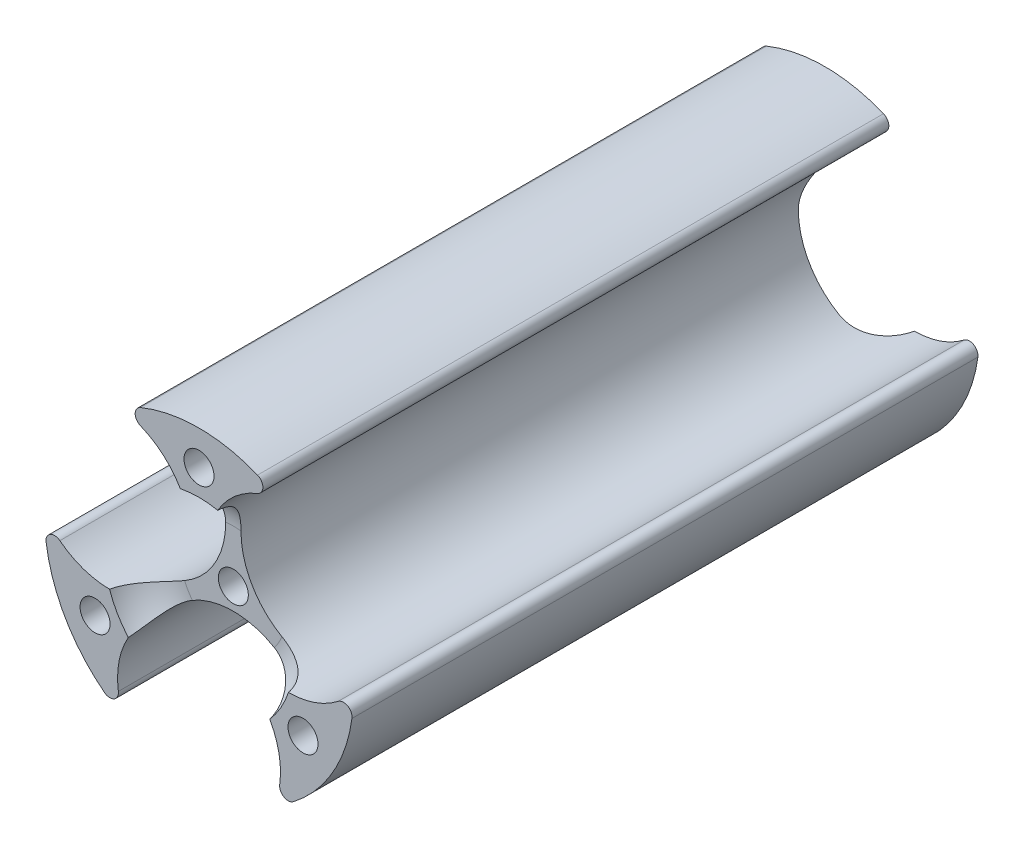
SolidWorks part; units mm, degrees
material "ABS"
ref_plane "Спереди" through (0, 0, 0) normal (0, 0, 1) x (1, 0, 0)
ref_plane "Сверху" through (0, 0, 0) normal (0, 1, 0) x (1, 0, 0)
ref_plane "Справа" through (0, 0, 0) normal (1, 0, 0) x (0, 0, -1)
sketch "Эскиз1" plane through (0, 0, 0) normal (0, 0, 1) x (1, 0, 0)
  line L0 (0, 0) -> (0, -18) construction
  line L1 (0, 0) -> (0, 18) construction
  circle A0 centre (0, 0) radius 18
  circle A1 centre (0, -12) radius 9.5
  circle A2 centre (-10.3923, 6) radius 9.5
  circle A3 centre (10.3923, 6) radius 9.5
  circle A4 centre (0, 14) radius 1.75
  circle A5 centre (12.1244, -7) radius 1.75
  circle A6 centre (-12.1244, -7) radius 1.75
  circle A7 centre (0, 0) radius 1.75
  point P13 (0, 0)
  point P20 (0, 0)
  dimension "D1" = 19
  dimension "D4" = 36
  dimension "D5" = 3.5
  dimension "D7" = 3.5
  dimension "D2" = 12
  dimension "D6" = 14
  dimension "D3" = 3
extrude "Бобышка-Вытянуть1" add sketch "Эскиз1" along normal blind 65 contours A3 A0 A2 A1 region at (15.086, -8.8822, 0)
fillet "Скругление1" radius 1 6 edges at (17.9974, 0.3068, 32.5) (8.733, -15.7396, 32.5) (-8.733, -15.7396, 32.5) (-17.9974, 0.3068, 32.5) (-9.2644, 15.4328, 32.5) (9.2644, 15.4328, 32.5)
sketch "Эскиз2" plane through (0, 0, 65) normal (0, 0, 1) x (1, 0, 0)
  arc A0 (6.8256, 16.6557) -> (-6.8256, 16.6557) centre (0, 0) ccw
  circle A1 centre (0, 14) radius 1.75
  circle A2 centre (0, 14) radius 1.75
  circle A3 centre (10.3923, 6) radius 9.5
  arc A4 (6.8222, 14.8037) -> (16.2314, -1.4936) centre (10.3923, 6) ccw
  circle A5 centre (-10.3923, 6) radius 9.5
  arc A6 (-16.2314, -1.4936) -> (-6.8222, 14.8037) centre (-10.3923, 6) ccw
  circle A7 centre (0, -12) radius 9.5
  arc A8 (9.4092, -13.31) -> (-9.4092, -13.31) centre (0, -12) ccw
  circle A9 centre (0, 0) radius 18
  arc A10 (-17.837, -2.4167) -> (-11.0114, -14.239) centre (0, 0) ccw
  circle A11 centre (0, 0) radius 1.75
  arc A12 (11.0114, -14.239) -> (17.837, -2.4167) centre (0, 0) ccw
  arc A13 (17.837, -2.4167) -> (16.2314, -1.4936) centre (16.8461, -2.2824) ccw
  arc A14 (6.8222, 14.8037) -> (16.2314, -1.4936) centre (10.3923, 6) ccw
  arc A15 (6.8222, 14.8037) -> (6.8256, 16.6557) centre (6.4464, 15.7304) ccw
  arc A16 (6.8256, 16.6557) -> (-6.8256, 16.6557) centre (0, 0) ccw
  arc A17 (-6.8256, 16.6557) -> (-6.8222, 14.8037) centre (-6.4464, 15.7304) ccw
  arc A18 (-16.2314, -1.4936) -> (-6.8222, 14.8037) centre (-10.3923, 6) ccw
  arc A19 (-16.2314, -1.4936) -> (-17.837, -2.4167) centre (-16.8461, -2.2824) ccw
  arc A20 (-17.837, -2.4167) -> (-11.0114, -14.239) centre (0, 0) ccw
  arc A21 (-11.0114, -14.239) -> (-9.4092, -13.31) centre (-10.3997, -13.4479) ccw
  arc A22 (9.4092, -13.31) -> (-9.4092, -13.31) centre (0, -12) ccw
  arc A23 (9.4092, -13.31) -> (11.0114, -14.239) centre (10.3997, -13.4479) ccw
  arc A24 (11.0114, -14.239) -> (17.837, -2.4167) centre (0, 0) ccw
  arc A25 (17.837, -2.4167) -> (16.2314, -1.4936) centre (16.8461, -2.2824) ccw
  arc A26 (6.8222, 14.8037) -> (16.2314, -1.4936) centre (10.3923, 6) ccw
  arc A27 (6.8222, 14.8037) -> (6.8256, 16.6557) centre (6.4464, 15.7304) ccw
  arc A28 (6.8256, 16.6557) -> (-6.8256, 16.6557) centre (0, 0) ccw
  arc A29 (-6.8256, 16.6557) -> (-6.8222, 14.8037) centre (-6.4464, 15.7304) ccw
  arc A30 (-16.2314, -1.4936) -> (-6.8222, 14.8037) centre (-10.3923, 6) ccw
  arc A31 (-16.2314, -1.4936) -> (-17.837, -2.4167) centre (-16.8461, -2.2824) ccw
  arc A32 (-17.837, -2.4167) -> (-11.0114, -14.239) centre (0, 0) ccw
  arc A33 (-11.0114, -14.239) -> (-9.4092, -13.31) centre (-10.3997, -13.4479) ccw
  arc A34 (9.4092, -13.31) -> (-9.4092, -13.31) centre (0, -12) ccw
  arc A35 (9.4092, -13.31) -> (11.0114, -14.239) centre (10.3997, -13.4479) ccw
  circle A36 centre (0, 0) radius 1.75
  circle A37 centre (-12.1244, -7) radius 1.75
  circle A38 centre (-12.1244, -7) radius 1.75
  circle A39 centre (12.1244, -7) radius 1.75
  circle A40 centre (12.1244, -7) radius 1.75
  arc A41 (11.0114, -14.239) -> (17.837, -2.4167) centre (0, 0) ccw
  circle A42 centre (0, 0) radius 11
  circle M23 centre (-12.1244, -7) radius 1.75
  circle M24 centre (12.1244, -7) radius 1.75
  circle M25 centre (0, 14) radius 1.75
  arc M26 (11.0114, -14.239) -> (17.837, -2.4167) centre (0, 0) ccw
  arc M27 (17.837, -2.4167) -> (16.2314, -1.4936) centre (16.8461, -2.2824) ccw
  arc M28 (16.2314, -1.4936) -> (6.8222, 14.8037) centre (10.3923, 6) cw
  arc M29 (6.8222, 14.8037) -> (6.8256, 16.6557) centre (6.4464, 15.7304) ccw
  arc M30 (6.8256, 16.6557) -> (-6.8256, 16.6557) centre (0, 0) ccw
  arc M31 (-6.8256, 16.6557) -> (-6.8222, 14.8037) centre (-6.4464, 15.7304) ccw
  arc M32 (-6.8222, 14.8037) -> (-16.2314, -1.4936) centre (-10.3923, 6) cw
  arc M33 (-16.2314, -1.4936) -> (-17.837, -2.4167) centre (-16.8461, -2.2824) ccw
  arc M34 (-17.837, -2.4167) -> (-11.0114, -14.239) centre (0, 0) ccw
  arc M35 (-11.0114, -14.239) -> (-9.4092, -13.31) centre (-10.3997, -13.4479) ccw
  arc M36 (-9.4092, -13.31) -> (9.4092, -13.31) centre (0, -12) cw
  arc M37 (9.4092, -13.31) -> (11.0114, -14.239) centre (10.3997, -13.4479) ccw
  dimension "D10" = 22
  dimension "D1" = 0
  dimension "D2" = 0
  dimension "D3" = 0
  dimension "D4" = 0
  dimension "D5" = 0
  dimension "D6" = 0
  dimension "D7" = 0
  dimension "D8" = 0
  dimension "D9" = 0
extrude "Бобышка-Вытянуть2" add sketch "Эскиз2" along normal blind 4 contours A42 M28 M29 M30 M31 M32 M25 | A42 M36 M37 M26 M27 M28 M24 | A42 M32 M33 M34 M35 M36 M23 region at (7.2809, 15.7288, 65) region at (17.2633, -1.5568, 65) region at (-13.5497, -3.1325, 65)
fillet "Скругление2" radius 5 3 edges at (-9.5263, -5.5, 65) (9.5263, -5.5, 65) (0, 11, 65)
sketch "Эскиз3" plane through (0, 0, 0) normal (0, 0, -1) x (-1, 0, 0)
  arc A0 (-17.837, -2.4167) -> (-11.0114, -14.239) centre (0, 0) ccw construction
  circle A1 centre (0, 0) radius 11
  circle A2 centre (0, 0) radius 11
  circle A3 centre (0, 14) radius 1.75
  circle A4 centre (0, 14) radius 1.75
  circle A5 centre (12.1244, -7) radius 1.75
  circle A6 centre (12.1244, -7) radius 1.75
  circle A7 centre (0, 0) radius 1.75
  circle A8 centre (0, 0) radius 1.75
  circle A9 centre (-12.1244, -7) radius 1.75
  circle A10 centre (-12.1244, -7) radius 1.75
  arc A11 (-16.2314, -1.4936) -> (-17.837, -2.4167) centre (-16.8461, -2.2824) ccw construction
  arc A12 (-17.837, -2.4167) -> (-11.0114, -14.239) centre (0, 0) ccw construction
  arc A13 (-11.0114, -14.239) -> (-9.4092, -13.31) centre (-10.3997, -13.4479) ccw construction
  arc A14 (-16.2314, -1.4936) -> (-6.8222, 14.8037) centre (-10.3923, 6) ccw construction
  arc A15 (-16.2314, -1.4936) -> (-6.8222, 14.8037) centre (-10.3923, 6) ccw construction
  arc A16 (-6.8256, 16.6557) -> (-6.8222, 14.8037) centre (-6.4464, 15.7304) ccw construction
  arc A17 (6.8256, 16.6557) -> (-6.8256, 16.6557) centre (0, 0) ccw construction
  arc A18 (6.8256, 16.6557) -> (-6.8256, 16.6557) centre (0, 0) ccw construction
  arc A19 (6.8222, 14.8037) -> (6.8256, 16.6557) centre (6.4464, 15.7304) ccw construction
  arc A20 (11.0114, -14.239) -> (17.837, -2.4167) centre (0, 0) ccw construction
  arc A21 (11.0114, -14.239) -> (17.837, -2.4167) centre (0, 0) ccw construction
  arc A22 (9.4092, -13.31) -> (11.0114, -14.239) centre (10.3997, -13.4479) ccw construction
  arc A23 (17.837, -2.4167) -> (16.2314, -1.4936) centre (16.8461, -2.2824) ccw construction
  arc A24 (9.4092, -13.31) -> (-9.4092, -13.31) centre (0, -12) ccw construction
  arc A25 (9.4092, -13.31) -> (-9.4092, -13.31) centre (0, -12) ccw construction
  arc A26 (6.8222, 14.8037) -> (16.2314, -1.4936) centre (10.3923, 6) ccw construction
  arc A27 (6.8222, 14.8037) -> (16.2314, -1.4936) centre (10.3923, 6) ccw construction
  arc A28 (-17.837, -2.4167) -> (-11.0114, -14.239) centre (0, 0) ccw
  arc A29 (-16.2314, -1.4936) -> (-17.837, -2.4167) centre (-16.8461, -2.2824) ccw
  arc A30 (-17.837, -2.4167) -> (-11.0114, -14.239) centre (0, 0) ccw
  arc A31 (-11.0114, -14.239) -> (-9.4092, -13.31) centre (-10.3997, -13.4479) ccw
  arc A32 (-16.2314, -1.4936) -> (-6.8222, 14.8037) centre (-10.3923, 6) ccw
  arc A33 (-16.2314, -1.4936) -> (-6.8222, 14.8037) centre (-10.3923, 6) ccw
  arc A34 (-6.8256, 16.6557) -> (-6.8222, 14.8037) centre (-6.4464, 15.7304) ccw
  arc A35 (6.8256, 16.6557) -> (-6.8256, 16.6557) centre (0, 0) ccw
  arc A36 (6.8256, 16.6557) -> (-6.8256, 16.6557) centre (0, 0) ccw
  arc A37 (6.8222, 14.8037) -> (6.8256, 16.6557) centre (6.4464, 15.7304) ccw
  arc A38 (11.0114, -14.239) -> (17.837, -2.4167) centre (0, 0) ccw
  arc A39 (11.0114, -14.239) -> (17.837, -2.4167) centre (0, 0) ccw
  arc A40 (9.4092, -13.31) -> (11.0114, -14.239) centre (10.3997, -13.4479) ccw
  arc A41 (17.837, -2.4167) -> (16.2314, -1.4936) centre (16.8461, -2.2824) ccw
  arc A42 (9.4092, -13.31) -> (-9.4092, -13.31) centre (0, -12) ccw
  arc A43 (9.4092, -13.31) -> (-9.4092, -13.31) centre (0, -12) ccw
  arc A44 (6.8222, 14.8037) -> (16.2314, -1.4936) centre (10.3923, 6) ccw
  arc A45 (6.8222, 14.8037) -> (16.2314, -1.4936) centre (10.3923, 6) ccw
  circle M7 centre (12.1244, -7) radius 1.75
  circle M8 centre (-12.1244, -7) radius 1.75
  circle M9 centre (0, 14) radius 1.75
  arc M10 (-6.8222, 14.8037) -> (-16.2314, -1.4936) centre (-10.3923, 6) cw
  arc M11 (-16.2314, -1.4936) -> (-17.837, -2.4167) centre (-16.8461, -2.2824) ccw
  arc M12 (-17.837, -2.4167) -> (-11.0114, -14.239) centre (0, 0) ccw
  arc M13 (-11.0114, -14.239) -> (-9.4092, -13.31) centre (-10.3997, -13.4479) ccw
  arc M14 (-9.4092, -13.31) -> (9.4092, -13.31) centre (0, -12) cw
  arc M15 (9.4092, -13.31) -> (11.0114, -14.239) centre (10.3997, -13.4479) ccw
  arc M16 (11.0114, -14.239) -> (17.837, -2.4167) centre (0, 0) ccw
  arc M17 (17.837, -2.4167) -> (16.2314, -1.4936) centre (16.8461, -2.2824) ccw
  arc M18 (16.2314, -1.4936) -> (6.8222, 14.8037) centre (10.3923, 6) cw
  arc M19 (6.8222, 14.8037) -> (6.8256, 16.6557) centre (6.4464, 15.7304) ccw
  arc M20 (6.8256, 16.6557) -> (-6.8256, 16.6557) centre (0, 0) ccw
  arc M21 (-6.8256, 16.6557) -> (-6.8222, 14.8037) centre (-6.4464, 15.7304) ccw
  dimension "D1" = 0
  dimension "D2" = 0
  dimension "D3" = 0
  dimension "D4" = 0
  dimension "D5" = 0
extrude "Бобышка-Вытянуть3" add sketch "Эскиз3" along normal blind 4 contours A2 M18 M19 M20 M21 M10 M9 | A2 M10 M11 M12 M13 M14 M8 | A2 M14 M15 M16 M17 M18 M7 region at (0, 11.1655, 0) region at (-13.5497, -3.1325, 0) region at (9.6674, -5.5815, 0)
fillet "Скругление3" radius 5 3 edges at (9.5263, -5.5, 0) (0, 11, 0) (-9.5263, -5.5, 0)
